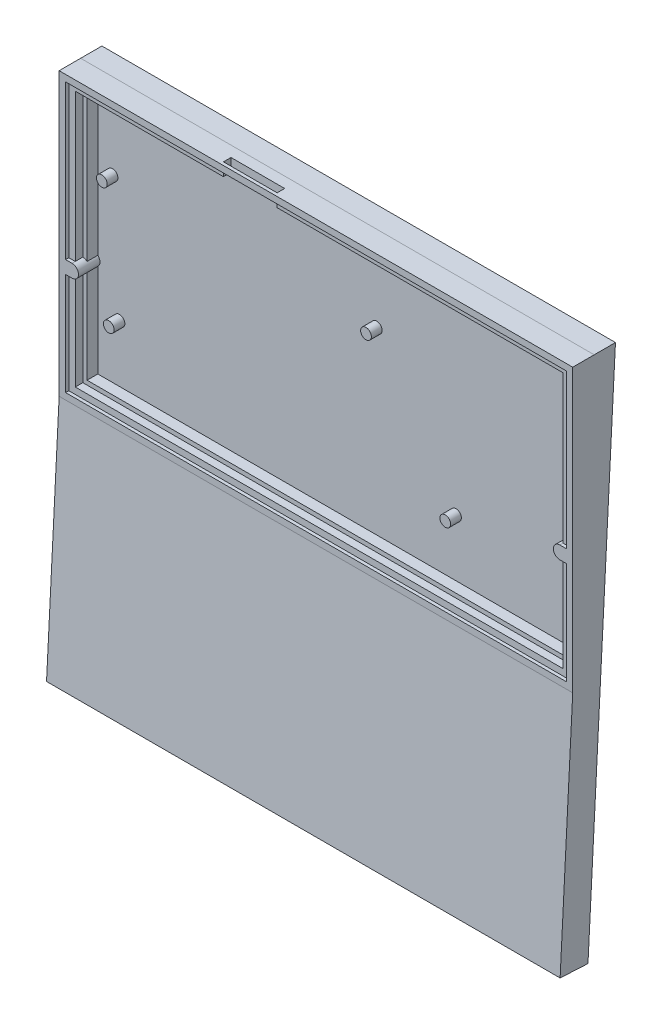
SolidWorks part; units mm, degrees
ref_plane "前视基准面" through (0, 0, 0) normal (0, 0, 1) x (1, 0, 0)
ref_plane "上视基准面" through (0, 0, 0) normal (0, 1, 0) x (1, 0, 0)
ref_plane "右视基准面" through (0, 0, 0) normal (1, 0, 0) x (0, 0, -1)
sketch "Model" plane through (0, 0, 0) normal (0, 0, 1) x (1, 0, 0)
  line L0 (675.8758, 289.5359) -> (675.8758, 217.8613)
  line L1 (672.8758, 286.5359) -> (672.8758, 217.8613)
  line L2 (670.8758, 284.5359) -> (670.8758, 217.0974)
  line L3 (675.8758, 211.8613) -> (675.8758, 164.2356)
  line L4 (675.8758, 164.2356) -> (442.7618, 164.2356)
  line L5 (678.8758, 292.5345) -> (678.8758, 161.2356)
  line L6 (678.8758, 161.2356) -> (439.7618, 161.2356)
  line L7 (672.8758, 211.8613) -> (672.8758, 167.2356)
  line L8 (672.8758, 167.2356) -> (445.7618, 167.2356)
  line L9 (670.8758, 212.6252) -> (670.8758, 169.2356)
  line L10 (670.8758, 169.2356) -> (447.7618, 169.2356)
  line L11 (442.7618, 289.5359) -> (675.8758, 289.5359)
  line L12 (445.7618, 286.5359) -> (672.8758, 286.5359)
  line L13 (447.7618, 284.5359) -> (670.8758, 284.5359)
  line L14 (442.7618, 164.2356) -> (442.7618, 211.8613)
  line L15 (445.7618, 167.2356) -> (445.7618, 211.8613)
  line L16 (447.7618, 169.2356) -> (447.7618, 212.6252)
  line L17 (442.7618, 217.8613) -> (442.7618, 289.5359)
  line L18 (439.7618, 161.2356) -> (439.7618, 292.5359)
  line L19 (445.7618, 217.8613) -> (445.7618, 286.5359)
  line L20 (447.7618, 217.0974) -> (447.7618, 284.5359)
  line L21 (675.8758, 211.8613) -> (672.8758, 211.8613)
  line L22 (675.8758, 217.8613) -> (672.8758, 217.8613)
  line L23 (442.7618, 217.8613) -> (445.7618, 217.8613)
  line L24 (445.7618, 211.8613) -> (442.7618, 211.8613)
  line L25 (675.8758, 217.8613) -> (675.8758, 289.5359)
  line L26 (439.7618, 161.2356) -> (678.8758, 161.2356)
  line L27 (439.7618, 161.2356) -> (439.7618, 292.5345)
  line L28 (514.7618, 286.5359) -> (539.7618, 286.5359)
  line L29 (439.7618, 292.5345) -> (678.8758, 292.5345)
  line L30 (439.7618, 292.5359) -> (678.8758, 292.5345)
  line L31 (678.8758, 161.2356) -> (678.8758, 292.5345)
  arc A0 (672.8758, 217.8613) -> (672.8758, 211.8613) centre (672.8758, 214.8613) ccw
  arc A1 (445.7618, 211.8613) -> (445.7618, 217.8613) centre (445.7618, 214.8613) ccw
  circle A2 centre (457.8498, 195.8116) radius 1.5
  circle A3 centre (577.6247, 252.9613) radius 1.5
  circle A4 centre (614.5337, 195.8116) radius 1.5
extrude "凸台-拉伸2" add sketch "Model" along normal blind 10 contours L29 L18 L6 L5 A1 L23 L17 L11 L0 L22 A0 L21 L3 L4 L14 L24 region at (676.1479, 226.8851, 0)
extrude "凸台-拉伸3" add sketch "Model<4>" along normal blind 8.5 contours L15 L24 L14 L4 L3 L21 L7 L8 | L17 L23 L19 L12 L1 L22 L0 L11 region at (673.437, 253.6986, 0) region at (674.3758, 209.482, 0)
sketch "Model<4>" plane through (0, 0, 0) normal (0, 0, 1) x (1, 0, 0) same geometry as "Model"
extrude "凸台-拉伸4" add sketch "Model<5>" along normal blind 5 contours A1 L15 L8 L7 A0 L9 L10 L16 | A1 L20 L13 L2 A0 L1 L12 L19 region at (670.9579, 219.8824, 0) region at (670.979, 209.8952, 0)
sketch "Model<5>" plane through (0, 0, 0) normal (0, 0, 1) x (1, 0, 0) same geometry as "Model"
sketch "草图3" plane through (0, 0, 0) normal (0, 0, -1) x (-1, 0, 0)
  circle A0 centre (-577.6247, 252.9613) radius 2.5
  circle A1 centre (-614.5337, 195.8116) radius 2.5
  circle A2 centre (-457.8498, 195.8116) radius 2.5
  circle A3 centre (-454.6247, 252.9613) radius 2.5
  dimension "D1" = 123
extrude "凸台-拉伸5" add sketch "草图3" against normal blind 5 separate body
sketch "草图4" plane through (439.7618, 0, 0) normal (-1, 0, 0) x (0, 0, 1)
  line L1 (-9.899, 292.5355) -> (2.8903, 48.5011)
  line L4 (10, 161.2356) -> (0, 161.2356)
  line L5 (0, 161.2356) -> (0, 292.5345)
  line L6 (10, 161.2356) -> (15.8725, 49.1815)
  line L7 (15.8725, 49.1815) -> (2.8903, 48.5011)
  line L8 (-9.899, 292.5355) -> (0, 292.5345)
  dimension "D1" = 3
  dimension "D3" = 13
extrude "凸台-拉伸6" add sketch "草图4" against normal up to surface (239.114 mm away) up to face at (678.8758, 226.8851, 5)
sketch "草图5" plane through (0, 0, 8.5) normal (0, 0, 1) x (1, 0, 0)
  line L0 (445.7618, 286.5359) -> (672.8758, 286.5359) construction
  line L1 (539.7618, 286.5359) -> (514.7618, 286.5359)
  line L2 (539.7618, 286.5359) -> (539.7618, 292.5345)
  line L3 (539.7618, 292.5345) -> (514.7618, 292.5345)
  line L4 (514.7618, 286.5359) -> (514.7618, 292.5345)
  line L5 (439.7618, 292.5345) -> (678.8758, 292.5345) construction
  dimension "D1" = 25
  dimension "D2" = 69
extrude "切除-拉伸1" cut sketch "草图5" against normal blind 3.5
